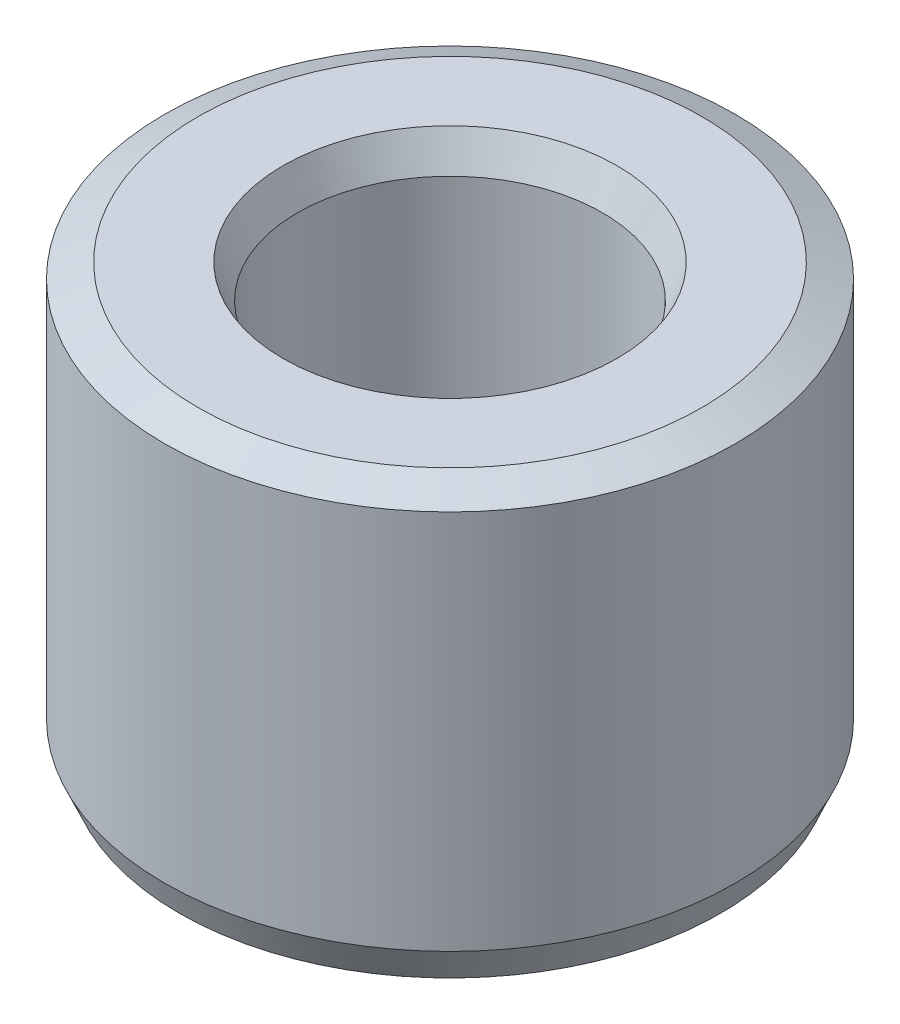
SolidWorks part; units mm, degrees
ref_plane "Front Plane" through (0, 0, 0) normal (0, 0, 1) x (1, 0, 0)
ref_plane "Top Plane" through (0, 0, 0) normal (0, 1, 0) x (1, 0, 0)
ref_plane "Right Plane" through (0, 0, 0) normal (1, 0, 0) x (0, 0, -1)
sketch "Sketch1" plane through (0, 0, 0) normal (0, 1, 0) x (1, 0, 0)
  circle A0 centre (0, 0) radius 60
  dimension "SLEEVE_OD" = 120
extrude "Boss-Extrude1" add sketch "Sketch1" along normal blind 90.1202
sketch "Sketch2" plane through (0, 0, 0) normal (0, 1, 0) x (1, 0, 0)
  circle A0 centre (0, 0) radius 32.0389
  dimension "BORE_D" = 64.0778
extrude "Cut-Extrude1" cut sketch "Sketch2" along normal through all
chamfer "Chamfer1" distance 3.0778 angle 66.311 4 edges at (0, 90.1202, 32.0389) (0, 0, 32.0389) (0, 0, 60) (0, 90.1202, 60) first distance on face at (0, 90.1202, 32.0389) first distance on face at (0, 0, 32.0389) first distance on face at (0, 90.1202, 60)
